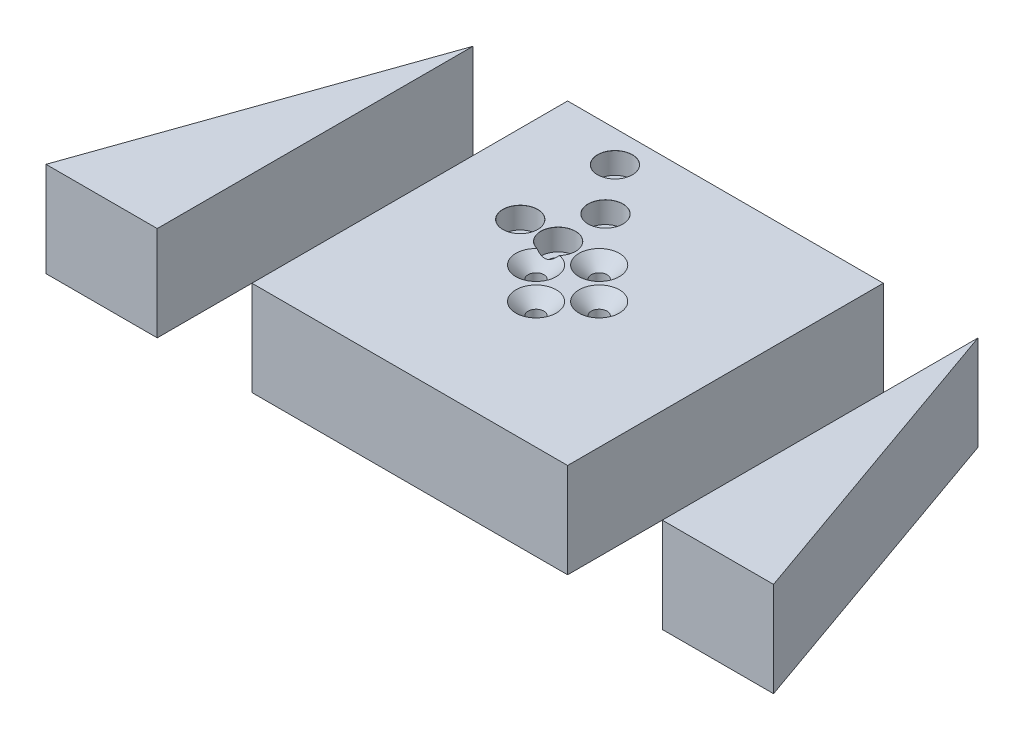
SolidWorks part; units mm, degrees
ref_plane "前视基准面" through (0, 0, 0) normal (0, 0, 1) x (1, 0, 0)
ref_plane "上视基准面" through (0, 0, 0) normal (0, 1, 0) x (1, 0, 0)
ref_plane "右视基准面" through (0, 0, 0) normal (1, 0, 0) x (0, 0, -1)
other "Configuration Table"
sketch "草图1" plane through (0, 0, 0) normal (0, 1, 0) x (1, 0, 0)
  line L5 (-50, 50) -> (50, 50)
  line L6 (-50, 50) -> (-50, -50)
  line L7 (-50, -50) -> (50, -50)
  line L8 (50, 50) -> (50, -50)
  line L9 (-50, 50) -> (50, -50) construction
  line L10 (-50, -50) -> (50, 50) construction
  line L13 (80, -50) -> (115.2355, -50)
  line L14 (115.2355, -50) -> (80, 50)
  line L15 (80, 50) -> (80, -50)
  point P0 (0, 0)
  dimension "D1" = 100
  dimension "D2" = 100
  dimension "D3" = 30
extrude "凸台-拉伸1" add sketch "草图1" along normal blind 30
hole_wizard "M6 六角圆柱头螺钉的柱形沉头孔2" positions "草图5" profile "草图6" counterbore size "M6" standard "GB" end condition through all
sketch "草图5" plane through (0, 30, 0) normal (0, 1, 0) x (1, 0, 0)
  line L0 (50, 50) -> (-50, 50) construction
  line L1 (-50, 50) -> (-50, -50) construction
  point P0 (-25, 10)
  point P11 (-30.0605, 6.9052)
  point P16 (0, 0)
  dimension "D1" = 40
  dimension "D2" = 25
sketch "草图6" plane through (-25, 30, -10) normal (1, 0, 0) x (0, 0, 1)
  line L0 (0, 0) -> (0, 30)
  line L1 (0, 30) -> (3.3, 30)
  line L3 (3.3, 30) -> (3.3, 6.8)
  line L4 (5.5, 6.8) -> (3.3, 6.8)
  line L5 (5.5, 6.8) -> (5.5, 0.025)
  line L6 (5.5, 0.025) -> (5.525, 0)
  line L7 (5.525, 0) -> (0, 0)
  line L8 (-5.5, 0.025) -> (-5.525, 0) construction
  line L11 (0, -6.35) -> (0, 107.95) construction
  dimension "通孔孔直径" = 6.6
  dimension "通孔孔深度" = 30
  dimension "柱形沉头孔直径" = 11
  dimension "柱形沉头孔深度" = 6.8
  dimension "近端锥形沉头孔直径" = 11.05
  dimension "近端锥形沉头孔角度" = 90
hole_wizard "M6 螺纹孔1" positions "草图7" profile "草图8" tap size "M6" standard "GB" end condition through all
sketch "草图7" plane through (0, 30, 0) normal (0, 1, 0) x (1, 0, 0)
  line L0 (-25, 10) -> (0, 10)
  line L1 (0, 10) -> (0, 0)
  point P0 (0, 10)
sketch "草图8" plane through (0, 30, -10) normal (1, 0, 0) x (0, 0, 1)
  line L0 (0, 0) -> (0, 30)
  line L1 (0, 30) -> (2.5, 30)
  line L2 (2.5, 30) -> (2.5, 3.9)
  line L3 (2.5, 3.9) -> (6.4, 0)
  line L5 (6.4, 0) -> (0, 0)
  line L6 (-2.5, 3.9) -> (-6.4, 0) construction
  line L11 (0, -6.35) -> (0, 107.95) construction
  dimension "通孔螺纹孔钻头直径" = 5
  dimension "通孔螺纹孔钻头深度" = 30
  dimension "近端锥形沉头孔直径" = 12.8
  dimension "近端锥形沉头孔角度" = 90
cosmetic thread "孔螺纹线1"
pattern_linear "阵列(线性)1" count 2 spacing 12 along (1, 0, 0) count 3 spacing 15 along (0, 0, -1) skipping (0, 1), (1, 2) of "M6 六角圆柱头螺钉的柱形沉头孔2"
ref_axis "基准轴1" through (0, 0, 0) along (0, 1, 0)
pattern_circular "阵列(圆周)1" count 4 every 90 about axis through (0, 0, 0) along (0, 1, 0) of "M6 螺纹孔1"
mirror "镜向1" about plane through (0, 0, 0) normal (1, 0, 0) of bodies 107
